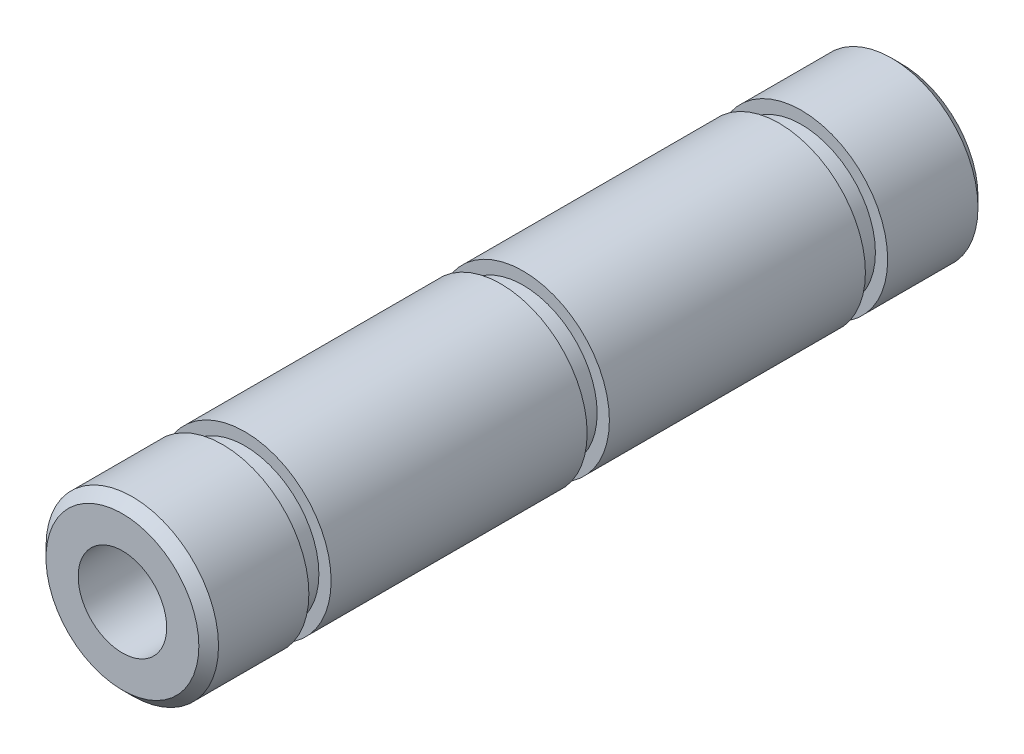
SolidWorks part; units mm, degrees
material "6061-T6 (SS)"
ref_plane "Front Plane" through (0, 0, 0) normal (0, 0, 1) x (1, 0, 0)
ref_plane "Top Plane" through (0, 0, 0) normal (0, 1, 0) x (1, 0, 0)
ref_plane "Right Plane" through (0, 0, 0) normal (1, 0, 0) x (0, 0, -1)
sketch "Sketch1" plane through (0, 0, 0) normal (0, 0, 1) x (1, 0, 0)
  circle A0 centre (0, 0) radius 9.8425
  circle A1 centre (0, 0) radius 5.0482
  dimension "D1" = 10.0965
  dimension "D2" = 19.685
  dimension "D3" = 4.7943
extrude "Boss-Extrude1" add sketch "Sketch1" against normal blind 88.9
sketch "Sketch2" plane through (0, 0, 0) normal (1, 0, 0) x (0, 0, -1)
  line L0 (88.9, 9.8425) -> (0, 9.8425) construction
  line L1 (43.18, 9.8425) -> (45.72, 9.8425)
  line L2 (43.18, 9.8425) -> (43.18, 8.4455)
  line L3 (43.18, 8.4455) -> (45.72, 8.4455)
  line L4 (45.72, 9.8425) -> (45.72, 8.4455)
  line L5 (0, 10.8268) -> (0, -10.8268) construction
  line L6 (74.93, 9.8425) -> (77.47, 9.8425)
  line L7 (74.93, 9.8425) -> (74.93, 8.4455)
  line L8 (74.93, 8.4455) -> (77.47, 8.4455)
  line L9 (77.47, 9.8425) -> (77.47, 8.4455)
  line L10 (11.43, 9.8425) -> (13.97, 9.8425)
  line L11 (11.43, 9.8425) -> (11.43, 8.4455)
  line L12 (11.43, 8.4455) -> (13.97, 8.4455)
  line L13 (13.97, 9.8425) -> (13.97, 8.4455)
  line L14 (88.9, -9.8425) -> (88.9, 9.8425) construction
  line L15 (0, 9.8425) -> (0, 8.72)
  line L16 (0, 8.72) -> (1.1225, 9.8425)
  line L17 (1.1225, 9.8425) -> (0, 9.8425)
  line L18 (87.7775, 9.8425) -> (88.9, 8.72)
  line L19 (88.9, 8.72) -> (88.9, 9.8425)
  line L20 (88.9, 9.8425) -> (87.7775, 9.8425)
  point P18 (44.45, 9.8425)
  dimension "D1" = 2.54
  dimension "D2" = 1.397
  dimension "D3" = 11.43
  dimension "D4" = 11.43
  dimension "D5" = 44.45
  dimension "D6" = 1.5875
  dimension "D7" = 1.5875
sketch "Sketch4" plane through (0, 0, 0) normal (1, 0, 0) x (0, 0, -1)
  line L0 (0, 0) -> (93.3245, 0) construction
revolve "Cut-Revolve1" cut sketch "Sketch2" angle 360 about L0
sketch "Sketch5" plane through (0, 0, 0) normal (0, 1, 0) x (1, 0, 0)
  line L0 (0, 0) -> (0, 93.3245) construction
  line L1 (-10.8268, 0) -> (10.8268, 0) construction
  line L2 (8.72, 88.9) -> (-8.72, 88.9) construction
  circle A0 centre (0, 19.05) radius 2.7051
  circle A1 centre (0, 69.85) radius 2.7051
  dimension "D1" = 5.4102
  dimension "D2" = 5.4102
  dimension "D3" = 19.05
  dimension "D4" = 19.05
extrude "Cut-Extrude1" cut sketch "Sketch5" against normal blind 88.9
ref_plane "Plane2" through (0, -9.8425, 0) normal (0, -1, 0) x (-1, 0, 0)
thread "Thread1" pitch 0.9071 method cut profile "Thread Profile2" start angle 0, offset 0, length 0, pitch 0.9071, diameter 5.4102
ref_plane "Plane3" through (2.7051, -9.8425, -19.05) normal (0, 0, 1) x (1, 0, 0)
sketch "Thread Profile2" plane through (2.7051, -9.8425, -19.05) normal (0, 0, 1) x (1, 0, 0)
  line L0 (0, 0) -> (0, 0.9071) construction
  line L1 (0, 0) -> (0.491, 0.2835)
  line L2 (0.491, 0.2835) -> (0.491, 0.3969)
  line L3 (0.491, 0.3969) -> (0, 0.6804)
  line L4 (0.491, 0.3402) -> (0, 0.3402) construction
  line L11 (0, 0) -> (0, 0.6804)
  point P2 (0, 0)
  dimension "Pitch" = 0.9071
  dimension "Profile_Angle" = 60
  dimension "Profile_Land" = 0.1134
  dimension "Profile_Height" = 0.491
thread "Thread2" pitch 0.9071 method cut profile "Thread Profile3" start angle 0, offset 0, length 0, pitch 0.9071, diameter 5.4102
ref_plane "Plane4" through (2.7051, -9.8425, -69.85) normal (0, 0, 1) x (1, 0, 0)
sketch "Thread Profile3" plane through (2.7051, -9.8425, -69.85) normal (0, 0, 1) x (1, 0, 0)
  line L0 (0, 0) -> (0, 0.9071) construction
  line L1 (0, 0) -> (0.491, 0.2835)
  line L2 (0.491, 0.2835) -> (0.491, 0.3969)
  line L3 (0.491, 0.3969) -> (0, 0.6804)
  line L4 (0.491, 0.3402) -> (0, 0.3402) construction
  line L11 (0, 0) -> (0, 0.6804)
  point P2 (0, 0)
  dimension "Pitch" = 0.9071
  dimension "Profile_Angle" = 60
  dimension "Profile_Land" = 0.1134
  dimension "Profile_Height" = 0.491
